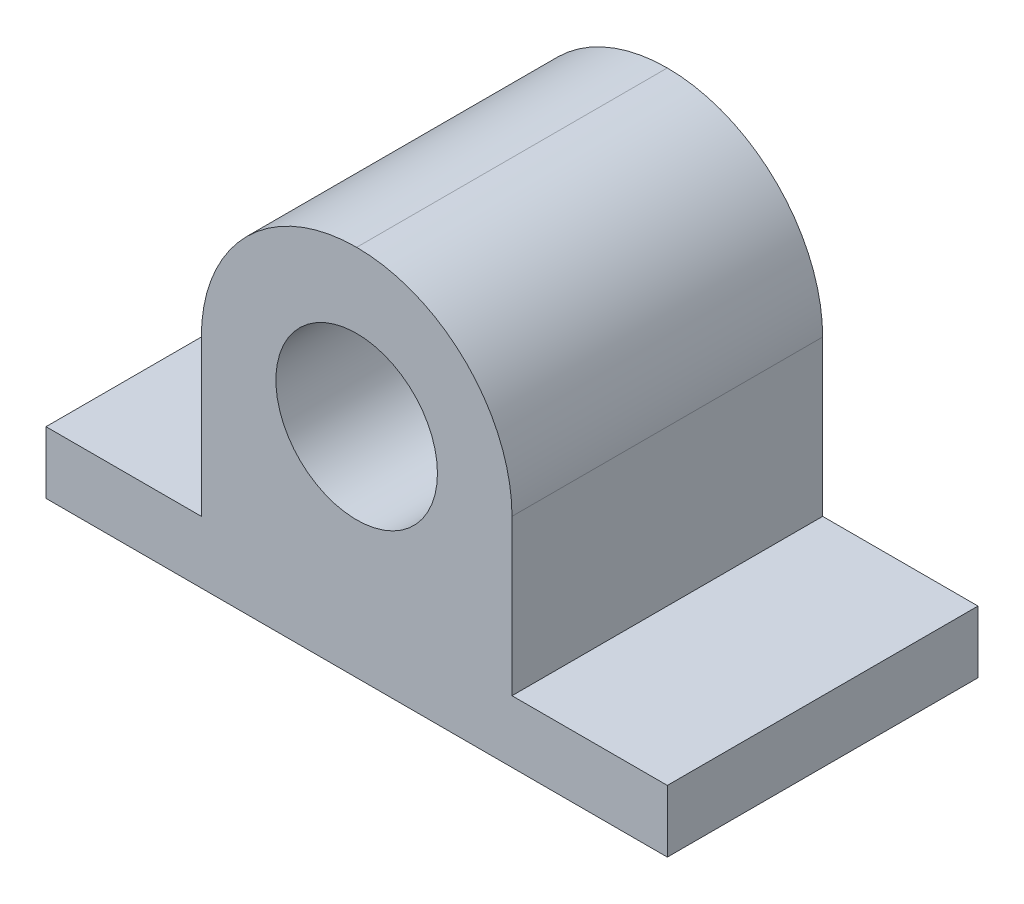
SolidWorks part; units mm, degrees
ref_plane "Alzado" through (0, 0, 0) normal (0, 0, 1) x (1, 0, 0)
ref_plane "Planta" through (0, 0, 0) normal (0, 1, 0) x (1, 0, 0)
ref_plane "Vista lateral" through (0, 0, 0) normal (1, 0, 0) x (0, 0, -1)
sketch "Croquis1" plane through (0, 0, 0) normal (0, 1, 0) x (1, 0, 0)
  line L1 (0, 0) -> (20, 0)
  line L2 (0, 0) -> (0, 10)
  line L3 (0, 10) -> (20, 10)
  line L4 (20, 0) -> (20, 10)
  dimension "D1" = 20
  dimension "D2" = 10
extrude "Saliente-Extruir1" add sketch "Croquis1" along normal blind 2
sketch "Croquis2" plane through (0, 0, 0) normal (0, 0, 1) x (1, 0, 0)
  line L0 (0, 2) -> (20, 2) construction
  line L1 (5, 2) -> (15, 2)
  line L2 (5, 2) -> (5, 12)
  line L3 (5, 12) -> (15, 12)
  line L4 (15, 2) -> (15, 12)
  line L5 (10, 12) -> (10, 0) construction
  line L6 (0, 0) -> (20, 0) construction
  line L7 (5, 12) -> (15, 2) construction
  circle A0 centre (10, 7) radius 2.6
  dimension "D3" = 5.2
  dimension "D1" = 10
  dimension "D2" = 10
extrude "Saliente-Extruir2" add sketch "Croquis2" against normal up to surface (10 mm away) up to face at (10, 1, -10)
fillet "Redondeo1" radius 5 2 edges at (15, 12, -5) (5, 12, -5)
